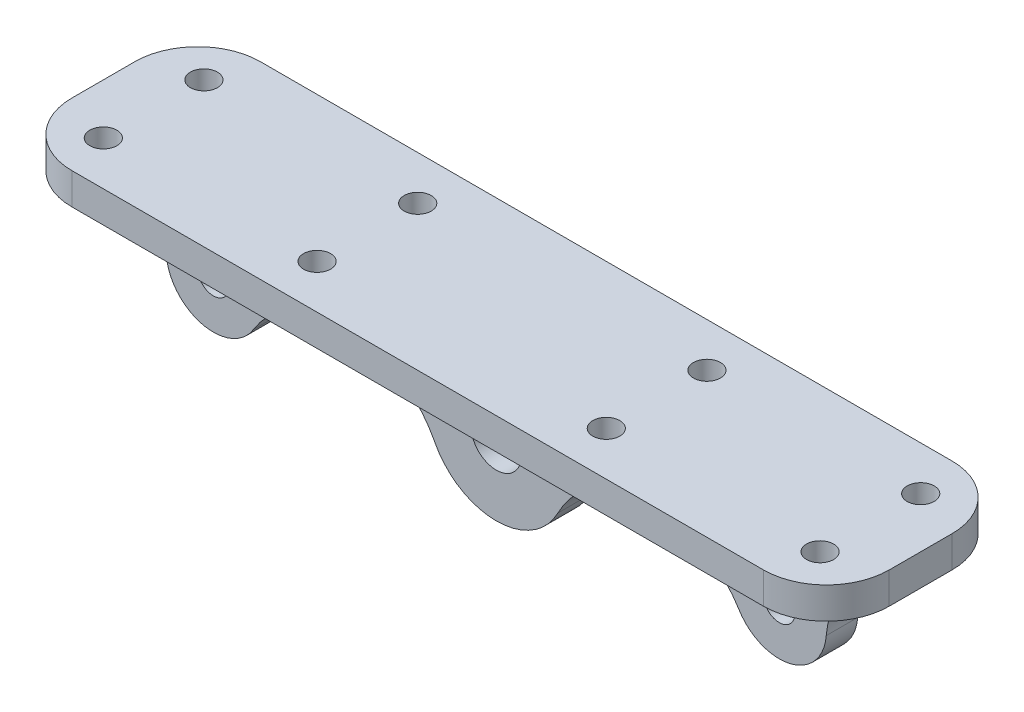
SolidWorks part; units mm, degrees
material "ABS"
ref_plane "Front Plane" through (0, 0, 0) normal (0, 0, 1) x (1, 0, 0)
ref_plane "Top Plane" through (0, 0, 0) normal (0, 1, 0) x (1, 0, 0)
ref_plane "Right Plane" through (0, 0, 0) normal (1, 0, 0) x (0, 0, -1)
sketch "Sketch1" plane through (0, 0, 0) normal (0, 0, 1) x (1, 0, 0)
  line L0 (0, -17.6791) -> (0, 20.5964) construction
  line L1 (0, 11) -> (0, -11)
  line L2 (-52.5, 11) -> (-52.5, 0)
  line L3 (0, 11) -> (-52.5, 11)
  circle A0 centre (0, 0) radius 4
  circle A1 centre (-45, 0) radius 2.5
  circle A2 centre (0, 0) radius 74.2 construction
  circle A3 centre (-45, 0) radius 7.5
  circle A4 centre (0, 0) radius 11
  arc A5 (-38.6142, -3.9333) -> (-9.7793, -5.0364) centre (-24.508, -12.6219) cw
  dimension "D1" = 8
  dimension "D2" = 5
  dimension "D4" = 148.4
  dimension "D5" = 22
  dimension "D6" = 15
  dimension "D3" = 45
extrude "Boss-Extrude1" add sketch "Sketch1" against normal mid plane 5 contours A3 A5 A4 L3 | A3 A1 | A3 L3 L2 | L1 A4 A0 region at (-27.5897, 6.8383, 0) region at (-5.1213, 0, 0) region at (-45, 7.2879, 0)
mirror "Mirror1" about plane through (0, 0, -2.5) normal (-1, 0, 0) of "Boss-Extrude1"
sketch "Sketch4" plane through (0, 11, 0) normal (0, 1, 0) x (1, 0, 0)
  line L0 (-52.5, 2.5) -> (-52.5, -2.5) construction
  line L1 (-65, -15) -> (65, -15)
  line L2 (-65, -15) -> (-65, 15)
  line L3 (-65, 15) -> (65, 15)
  line L4 (65, -15) -> (65, 15)
  line L6 (52.5, -2.5) -> (-52.5, -2.5) construction
  line L7 (52.5, 2.5) -> (-52.5, 2.5) construction
  dimension "D1" = 130
  dimension "D2" = 12.5
  dimension "D3" = 12.5
  dimension "D4" = 12.5
extrude "Boss-Extrude2" add sketch "Sketch4" along normal blind 5
fillet "Fillet1" radius 10 4 edges at (-65, 13.5, 15) (-65, 13.5, -15) (65, 13.5, -15) (65, 13.5, 15)
fillet "Fillet2" radius 12.5 2 edges at (-52.5, 11, 0) (52.5, 11, 0)
sketch "Sketch5" plane through (0, 16, 0) normal (0, 1, 0) x (1, 0, 0)
  line L1 (-55, -15) -> (55, -15) construction
  line L2 (55, 15) -> (-55, 15) construction
  line L3 (-65, 5) -> (-65, -5) construction
  circle A0 centre (-57, -8) radius 2.15
  circle A1 centre (-57, 8) radius 2.15
  circle A6 centre (-23, -8) radius 2.15
  circle A7 centre (-23, 8) radius 2.15
  dimension "D2" = 34
  dimension "D3" = 4.3
  dimension "D4" = 4.3
  dimension "D6" = 4.3
  dimension "D11" = 4.3
  dimension "D7" = 7
  dimension "D8" = 8
  dimension "D9" = 8
  dimension "D10" = 7
extrude "Cut-Extrude1" cut sketch "Sketch5" against normal blind 10
mirror "Mirror2" about plane through (0, 0, 0) normal (1, 0, 0) of "Cut-Extrude1"
ref_plane "Plane1" through (36.5, 0, 0) normal (1, 0, 0) x (0, 0, -1)
sketch "Sketch7" plane through (36.5, 0, 0) normal (1, 0, 0) x (0, 0, -1)
  line L0 (-5, 11) -> (5, 11) construction
  line L1 (5, 16) -> (-5, 16) construction
  line L2 (-5, 16) -> (-5, 11) construction
  line L3 (15, 16) -> (5, 16) construction
  line L4 (5, 11) -> (15, 11) construction
  line L5 (15, 11) -> (15, 16) construction
  line L6 (2.5, -0.5625) -> (2.5, 11) construction
  line L7 (2.5, 11) -> (-2.5, 11) construction
  line L8 (-2.5, 11) -> (-2.5, -0.5625) construction
  line L9 (-2.5, -0.5625) -> (2.5, -0.5625) construction
  line L10 (-5, 11) -> (5, 11)
  line L11 (5, 16) -> (-5, 16)
  line L12 (-5, 16) -> (-5, 11)
  line L13 (15, 16) -> (5, 16)
  line L14 (5, 11) -> (15, 11)
  line L15 (15, 11) -> (15, 16)
  line L16 (2.5, -0.5625) -> (2.5, 11)
  line L17 (2.5, 11) -> (-2.5, 11)
  line L18 (-2.5, 11) -> (-2.5, -0.5625)
  line L19 (-2.5, -0.5625) -> (2.5, -0.5625)
  line L20 (2.5, 6) -> (7.5, 11)
  line L21 (2.5, 11) -> (7.5, 11)
  line L22 (2.5, 11) -> (2.5, 6)
  dimension "D1" = 5
  dimension "D2" = 5
extrude "Boss-Extrude3" add sketch "Sketch7" along normal mid plane 5 contours L16 L20 L14 L10 region at (36.5, 9.3333, -4.1667)
pattern_linear "LPattern1" count 2 spacing 23 along (-1, 0, 0) of "Boss-Extrude3"
mirror "Mirror4" about plane through (0, 0, 0) normal (0, 0, 1) of "LPattern1" second plane through (0, 0, 0) second plane normal (1, 0, 0)
